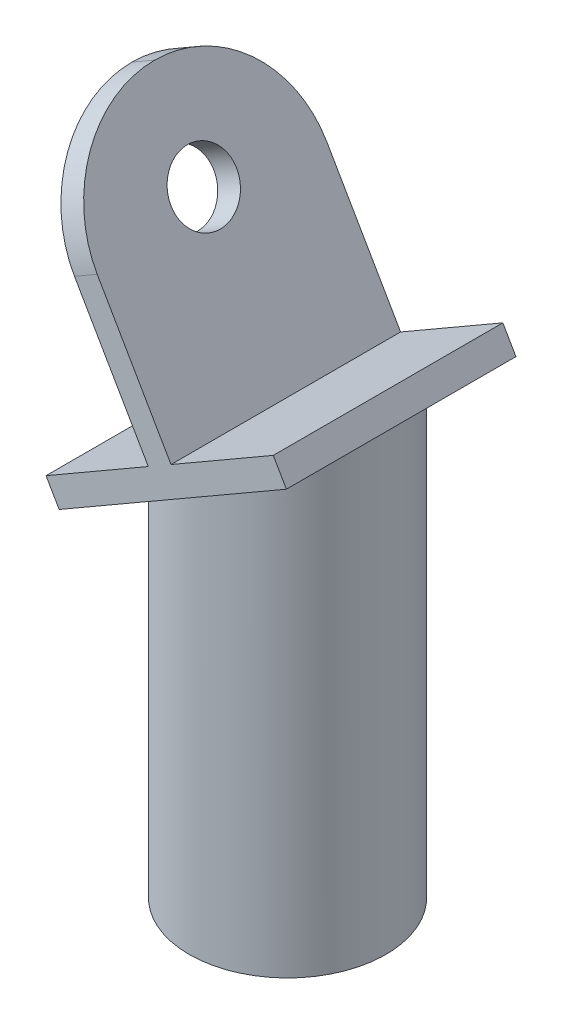
SolidWorks part; units mm, degrees
ref_plane "Front Plane" through (0, 0, 0) normal (0, 0, 1) x (1, 0, 0)
ref_plane "Top Plane" through (0, 0, 0) normal (0, 1, 0) x (1, 0, 0)
ref_plane "Right Plane" through (0, 0, 0) normal (1, 0, 0) x (0, 0, -1)
sketch "Sketch2" plane through (0, 0, 0) normal (0, 1, 0) x (1, 0, 0)
  circle A0 centre (0, 0) radius 15
  circle A1 centre (0, 0) radius 13
  dimension "D1" = 30
  dimension "D2" = 2
extrude "Boss-Extrude1" add sketch "Sketch2" along normal blind 70
sketch "Sketch3" plane through (0, 0, 0) normal (0, 0, 1) x (1, 0, 0)
  line L0 (-15, 0) -> (15, 0) construction
  line L1 (15, 70) -> (-15, 70) construction
  line L2 (-15, 0) -> (15, 0)
  line L3 (15, 70) -> (-15, 70)
  line L4 (15, 70) -> (-15, 52.6795)
  line L5 (-15, 70) -> (-15, 0) construction
  line L6 (-15, 52.6795) -> (-15, 70)
  dimension "D1" = 30
extrude "Cut-Extrude1" cut sketch "Sketch3" against normal through all both and the other way through all contours L6 L4 L3 region at (-5, 64.2265, 0)
sketch "Sketch4" plane through (-26.5609, 46.0048, 0) normal (-0.5, 0.866, 0) x (0.866, 0.5, 0)
  line L1 (10.6699, 17.5) -> (50.6699, 17.5)
  line L2 (10.6699, 17.5) -> (10.6699, -17.5)
  line L3 (10.6699, -17.5) -> (50.6699, -17.5)
  line L4 (50.6699, 17.5) -> (50.6699, -17.5)
  line L5 (10.6699, 17.5) -> (50.6699, -17.5) construction
  line L6 (10.6699, -17.5) -> (50.6699, 17.5) construction
  point P0 (30.6699, 0)
  point P5 (30.6699, 0)
  point P6 (0, 0)
  point P7 (0, 0)
  point P8 (0, 0)
  dimension "D1" = 35
  dimension "D2" = 40
extrude "Boss-Extrude2" add sketch "Sketch4" along normal blind 4
sketch "Sketch5" plane through (-28.5609, 49.4689, 0) normal (-0.5, 0.866, 0) x (0.866, 0.5, 0)
  line L0 (30.6699, 17.5) -> (30.6699, -17.5) construction
  line L1 (32.6699, 17.5) -> (28.6699, 17.5)
  line L2 (32.6699, 17.5) -> (32.6699, -17.5)
  line L3 (32.6699, -17.5) -> (28.6699, -17.5)
  line L4 (28.6699, 17.5) -> (28.6699, -17.5)
  line L5 (32.6699, 17.5) -> (28.6699, -17.5) construction
  line L6 (32.6699, -17.5) -> (28.6699, 17.5) construction
  line L7 (50.6699, 17.5) -> (10.6699, 17.5) construction
  line L8 (10.6699, -17.5) -> (50.6699, -17.5) construction
  point P0 (30.6699, 0)
  point P11 (0, 0)
  dimension "D1" = 4
extrude "Boss-Extrude4" add sketch "Sketch5" along normal blind 40
sketch "Sketch6" plane through (24.8288, 14.3349, 0) normal (-0.866, -0.5, 0) x (0, 0, 1)
  line L0 (-17.5, 57.1218) -> (17.5, 57.1218) construction
  circle A0 centre (0, 82.1218) radius 5
  dimension "D1" = 10
  dimension "D2" = 25
extrude "Cut-Extrude2" cut sketch "Sketch6" against normal through all
fillet "Fillet3" radius 17.5 2 edges at (-22, 99.4449, 17.5) (-22, 99.4449, -17.5)
